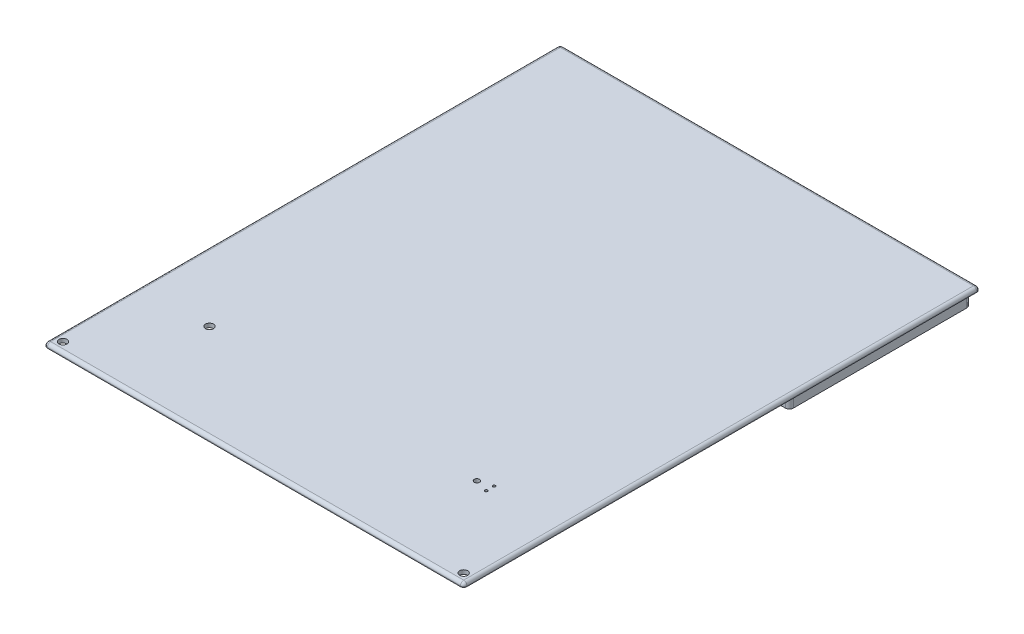
SolidWorks part; units mm, degrees
ref_plane "Front Plane" through (0, 0, 0) normal (0, 0, 1) x (1, 0, 0)
ref_plane "Top Plane" through (0, 0, 0) normal (0, 1, 0) x (1, 0, 0)
ref_plane "Right Plane" through (0, 0, 0) normal (1, 0, 0) x (0, 0, -1)
sketch "Sketch1" plane through (0, 0, 0) normal (0, 1, 0) x (1, 0, 0)
  line L0 (79.25, -36) -> (79.25, 36)
  line L1 (-78, -34.75) -> (78, -34.75)
  line L2 (-78, -34.75) -> (-78, 34.75)
  line L3 (-78, 34.75) -> (78, 34.75)
  line L4 (78, -34.75) -> (78, 34.75)
  line L5 (-78, -34.75) -> (78, 34.75) construction
  line L6 (-78, 34.75) -> (78, -34.75) construction
  line L7 (-79.25, 36) -> (79.25, 36)
  line L8 (-79.25, -36) -> (-79.25, 36)
  line L9 (-78, -36) -> (78, -36)
  line L10 (-78, -36) -> (-78, -86)
  line L11 (-78, -36) -> (78, -36)
  line L12 (-79.25, -36) -> (-79.25, -86)
  line L13 (-79.25, -86) -> (-79.25, -159)
  line L14 (79.25, -36) -> (79.25, -86)
  line L15 (78, -36) -> (78, -86)
  line L16 (-79.25, -36) -> (79.25, -36) construction
  line L17 (-78, -86) -> (-78, -100.5886)
  line L18 (79.25, -86) -> (79.25, -159)
  line L19 (78, -86) -> (78, -157.75)
  line L20 (79.25, -159) -> (-79.25, -159)
  line L21 (78, -159) -> (79.25, -159)
  line L22 (-78, -100.5886) -> (-78, -157.75)
  line L23 (-78, -157.75) -> (78, -157.75)
  line L24 (-78, -157.75) -> (78, -157.75) construction
  line L25 (0, -157.75) -> (0, -117.25)
  line L26 (-40, -117.25) -> (40, -117.25)
  line L27 (-34, -117.25) -> (34, -117.25)
  line L28 (-40, -117.25) -> (-34, -117.25) construction
  circle A0 centre (-37, -117.25) radius 3
  point P0 (0, 0)
  point P27 (0, -117.25)
  point P30 (0, -117.25)
  dimension "D1" = 156
  dimension "D2" = 69.5
  dimension "D4" = 50
  dimension "D5" = 195
  dimension "D6" = 1.25
  dimension "D7" = 40.5
  dimension "D8" = 80
  dimension "D9" = 68
  dimension "D3" = 1.25
sketch "Sketch2" plane through (0, 0, 0) normal (0, 1, 0) x (1, 0, 0)
  line L0 (-79.25, 36) -> (79.25, 36)
  line L1 (79.25, 36) -> (79.25, -159)
  line L2 (79.25, -159) -> (-79.25, -159)
  line L3 (-79.25, -159) -> (-79.25, 36)
extrude "Boss-Extrude1" add sketch "Sketch2" against normal blind 1.25
extrude "Boss-Extrude2" add sketch "Sketch1" along normal blind 105 contours L20 L18 L14 L0 L7 L8 L12 L13 L23 L22 L17 L10 L9 L15 L19 L4 L1 L2 L3 region at (78.9987, 0, 61)
sketch "Sketch4" plane through (0, 0, 0) normal (0, 1, 0) x (1, 0, 0)
  line L0 (-78, -157.75) -> (78, -157.75) construction
  line L1 (0, -157.75) -> (0, -117.75)
  line L2 (0, -5.0875) -> (0, 5.0875) construction
  line L3 (-34, -117.75) -> (34, -117.75)
  line L4 (-40.15, -117.75) -> (-39.575, -117.75)
  line L5 (-40.15, -117.75) -> (-39.575, -117.75) construction
  line L6 (34, -117.75) -> (34.575, -117.75) construction
  line L7 (-34.575, -117.75) -> (34.575, -117.75)
  line L8 (-34.575, -117.75) -> (-34, -117.75) construction
  line L9 (39.575, -117.75) -> (40.15, -117.75) construction
  line L10 (39.575, -117.75) -> (40.15, -117.75)
  circle A0 centre (-37.075, -117.75) radius 2.5
  circle A1 centre (37.075, -117.75) radius 2.5
  point P12 (0, -117.75)
  point P15 (0, -117.75)
  dimension "D1" = 40
  dimension "D2" = 68
  dimension "D3" = 80.3
extrude "Boss-Extrude3" add sketch "Sketch4" along normal blind 8 contours A0 | A1 region at (37.075, 0, 117.75) region at (-37.075, 0, 117.75)
fillet "Fillet2" radius 2 18 edges at (-78, 0, 0) (0, 0, -34.75) (78, 0, 0) (0, 0, 34.75) (0, 0, 36) (78, 0, 96.875) (0, 0, 157.75) (-78, 0, 96.875) (-37.075, 0, 115.25) (37.075, 0, 115.25) (78, 52.5, -34.75) (-78, 52.5, -34.75) (78, 52.5, 34.75) (-78, 52.5, 34.75) (-78, 52.5, 157.75) (78, 52.5, 157.75) (78, 52.5, 36) (-78, 52.5, 36)
sketch "Sketch5" plane through (0, 0, 36) normal (0, 0, 1) x (1, 0, 0)
  line L0 (-76, 105) -> (76, 105) construction
  line L2 (-76, 105) -> (-76, 2) construction
  line L3 (-58.75, 4.5) -> (58.75, 4.5)
  line L4 (-58.75, 4.5) -> (-58.75, 101.5)
  line L5 (-58.75, 101.5) -> (58.75, 101.5)
  line L6 (58.75, 4.5) -> (58.75, 101.5)
  line L7 (-58.75, 53) -> (58.75, 53)
  line L8 (-53.75, 101.5) -> (-53.75, 98)
  line L14 (-58.75, 98) -> (-53.75, 98)
  line L15 (0, 53) -> (0, 77.907)
  circle A0 centre (-53.75, 98) radius 1.55
  circle A1 centre (-53.75, 8) radius 1.55
  circle A2 centre (53.75, 8) radius 1.55
  circle A3 centre (53.75, 98) radius 1.55
  point P8 (0, 53.5)
  dimension "D1" = 97
  dimension "D2" = 117.5
  dimension "D3" = 17.25
  dimension "D4" = 3.5
  dimension "D5" = 5
  dimension "D6" = 3.5
extrude "Cut-Extrude1" cut sketch "Sketch5" against normal blind 8 contours L14 A0 L8 | L8 A0 L14 | A3 | A1 | A2 region at (-54.4078, 98.6578, 36) region at (-53.5307, 97.7807, 36) region at (-53.75, 8, 36) region at (53.75, 98, 36)
sketch "Sketch6" plane through (0, 0, 157.75) normal (0, 0, -1) x (-1, 0, 0)
  line L0 (-76, 2) -> (76, 2) construction
  line L1 (0, 2) -> (0, 22)
  line L2 (0, 5.0875) -> (0, -5.0875) construction
  circle A0 centre (0, 22) radius 8.25
  dimension "D1" = 20
extrude "Cut-Extrude2" cut sketch "Sketch6" against normal blind 8 contours A0 region at (-5.6686, 16.3314, 157.75)
sketch "Sketch8" plane through (-79.25, 0, 0) normal (-1, 0, 0) x (0, 0, 1)
  line L0 (159, 55) -> (116.5, 55)
  line L1 (159, -1.25) -> (159, 105) construction
  line L2 (116.5, 5) -> (116.5, 105)
  line L3 (159, 105) -> (-36, 105) construction
  line L4 (116.5, 55) -> (101.5, 55)
  line L5 (116.5, 55) -> (131.5, 55)
  line L7 (113, 58) -> (120, 58)
  line L8 (113, 58) -> (113, 72)
  line L9 (113, 72) -> (120, 72)
  line L10 (120, 58) -> (120, 72)
  line L11 (113, 58) -> (120, 72) construction
  line L12 (113, 72) -> (120, 58) construction
  circle A0 centre (101.5, 55) radius 3
  circle A1 centre (101.5, 65) radius 3
  circle A2 centre (101.5, 75) radius 3
  circle A3 centre (101.5, 85) radius 3
  circle A4 centre (131.5, 55) radius 3.75
  circle A5 centre (131.5, 75) radius 3.75
  point P9 (116.5, 55)
  point P13 (116.5, 65)
  dimension "D4" = 4
  dimension "D5" = 2
  dimension "D1" = 42.5
  dimension "D2" = 15
  dimension "D3" = 15
  dimension "D6" = 7
  dimension "D7" = 14
  dimension "D8" = 10
  dimension "D9" = 50
extrude "Cut-Extrude3" cut sketch "Sketch8" against normal blind 8 contours A0 | A2 | A3 | A1 | A5 | L8 L9 L10 L7 | A4 region at (-79.25, 55, 98.5849) region at (-79.25, 65, 101.5) region at (-79.25, 75, 101.5) region at (-79.25, 85, 101.5) region at (-79.25, 75, 131.5)
fillet "Fillet3" radius 1.25 4 edges at (0, -1.25, 159) (79.25, -1.25, 61.5) (0, -1.25, -36) (-79.25, -1.25, 61.5)
fillet "Fillet4" radius 1.25 8 edges at (-78.8839, -0.8839, 158.6339) (78.8839, -0.8839, 158.6339) (78.8839, -0.8839, -35.6339) (-78.8839, -0.8839, -35.6339) (-79.25, 52.5, 159) (79.25, 52.5, 159) (79.25, 52.5, -36) (-79.25, 52.5, -36)
sketch "Sketch11" plane through (79.25, 0, 0) normal (1, 0, 0) x (0, 0, -1)
  line L0 (-157.75, 105) -> (34.75, 0) construction
  line L1 (34.75, 105) -> (-157.75, 0)
  line L2 (87.175, 0) -> (-87.175, 0) construction
  line L4 (-111.5, 102.5) -> (-11.5, 102.5)
  line L5 (-111.5, 102.5) -> (-111.5, 2.5)
  line L6 (-111.5, 2.5) -> (-11.5, 2.5)
  line L7 (-11.5, 102.5) -> (-11.5, 2.5)
  line L8 (-111.5, 102.5) -> (-11.5, 2.5) construction
  line L9 (-111.5, 2.5) -> (-11.5, 102.5) construction
  line L10 (-99, 15) -> (-24, 15)
  line L11 (-99, 15) -> (-99, 90)
  line L12 (-99, 90) -> (-24, 90)
  line L13 (-24, 15) -> (-24, 90)
  line L14 (-99, 15) -> (-24, 90) construction
  line L15 (-99, 90) -> (-24, 15) construction
  circle A0 centre (-11.5, 102.5) radius 1.55
  circle A1 centre (-111.5, 102.5) radius 1.55
  circle A2 centre (-99, 90) radius 1.55
  circle A3 centre (-24, 90) radius 1.55
  circle A4 centre (-99, 15) radius 1.55
  circle A5 centre (-111.5, 2.5) radius 1.55
  circle A6 centre (-11.5, 2.5) radius 1.55
  circle A7 centre (-24, 15) radius 1.55
  point P9 (-61.5, 52.5)
  point P14 (-61.5, 52.5)
  dimension "D1" = 100
  dimension "D2" = 100
  dimension "D3" = 75
  dimension "D4" = 75
extrude "Cut-Extrude4" cut sketch "Sketch11" against normal blind 8 contours L7 A0 L4 | L4 A0 L7 | L13 A3 L12 | L12 A3 L13 | L6 A6 L7 | L5 A5 L6 | L6 A5 L5 | L11 A4 L10 | L10 A4 L11 | L10 A7 L13 | L13 A7 L10 | A1 | A2 | A6 region at (79.25, 101.8422, 12.1578) region at (79.25, 102.7193, 11.2807) region at (79.25, 2.2807, 11.2807) region at (79.25, 14.7807, 23.7807) region at (79.25, 15.6578, 24.6578) region at (79.25, 89.3422, 24.6578) region at (79.25, 90.2193, 23.7807) region at (79.25, 15.6578, 98.3422) region at (79.25, 14.7807, 99.2193) region at (79.25, 2.2807, 111.7193) region at (79.25, 3.1578, 110.8422)
sketch "Sketch12" plane through (0, 105, 0) normal (0, 1, 0) x (1, 0, 0)
  line L0 (0, -155.75) -> (0, -144.3132)
  line L1 (-78, -157.75) -> (-73, -157.75)
  line L2 (-78, -157.75) -> (-78, -152.75)
  line L3 (-78, -152.75) -> (-73, -152.75)
  line L4 (-73, -157.75) -> (-73, -152.75)
  line L5 (-76, -155.75) -> (76, -155.75) construction
  line L6 (0, -5.0875) -> (0, 5.0875) construction
  line L7 (78, -152.75) -> (73, -152.75)
  line L8 (73, -157.75) -> (73, -152.75)
  line L9 (78, -157.75) -> (73, -157.75)
  line L10 (78, -157.75) -> (78, -152.75)
  line M6 (76, -157.75) -> (-76, -157.75)
  arc M7 (-76, -157.75) -> (-78, -155.75) centre (-76, -155.75) cw
  line M8 (-78, -155.75) -> (-78, -38)
  line M12 (78, -38) -> (78, -155.75)
  arc M13 (78, -155.75) -> (76, -157.75) centre (76, -155.75) cw
  dimension "D1" = 5
  dimension "D2" = 5
extrude "Boss-Extrude5" add sketch "Sketch12" against normal up to surface (105 mm away) contours L8 L7 M6 M13 M12 | L4 L3 M6 M8 M7 region at (75.427, 105, 155.177) region at (-75.427, 105, 155.177) up to face at (0, 0, 96.875)
fillet "Fillet5" radius 1.25 14 edges at (78, 53.5, 152.75) (77.4142, 0.5858, 152.75) (74.5, 0, 152.75) (73, 0, 154.25) (73, 0.5858, 157.1642) (-73, 0, 154.25) (-73, 0.5858, 157.1642) (-74.5, 0, 152.75) (-77.4142, 0.5858, 152.75) (73, 53.5, 157.75) (73, 52.5, 152.75) (-73, 53.5, 157.75) (-78, 53.5, 152.75) (-73, 52.5, 152.75)
sketch "Sketch14" plane through (0, 105, 0) normal (0, 1, 0) x (1, 0, 0)
  line L0 (78, -38) -> (78, -151.5) construction
  line L1 (73.3661, -153.1161) -> (78, -153.1161)
  line L2 (73.3661, -153.1161) -> (73.3661, -157.75)
  line L3 (73.3661, -157.75) -> (78, -157.75)
  line L4 (78, -153.1161) -> (78, -157.75)
  line L5 (73.3661, -153.1161) -> (78, -157.75) construction
  line L6 (78, -157.75) -> (78.0536, -157.7607) construction
  line L7 (0, -157.75) -> (0, -147.0716)
  line L8 (-71.75, -157.75) -> (71.75, -157.75) construction
  line L9 (0, -58.4375) -> (0, 58.4375) construction
  arc A0 (74.25, -152.75) -> (73, -154) centre (74.25, -154) ccw construction
  circle A1 centre (75.6831, -155.4331) radius 1.525
  circle A2 centre (-75.6831, -155.4331) radius 1.525
extrude "Cut-Extrude5" cut sketch "Sketch14" against normal blind 8 contours A1 | A2 region at (75.6831, 105, 155.4331) region at (-75.6831, 105, 155.4331)
sketch "Sketch15" plane through (0, 105, 0) normal (0, 1, 0) x (1, 0, 0)
  line L16 (76, 33) -> (-76, 33)
  line L17 (-76.25, 32.75) -> (-76.25, -32.75)
  line L18 (-76, -33) -> (76, -33)
  line L19 (76.25, -32.75) -> (76.25, 32.75)
  line L20 (-77.5, 32.75) -> (-77.5, -32.75)
  line L21 (-76, -34.25) -> (76, -34.25)
  line L22 (77.5, -32.75) -> (77.5, 32.75)
  line L23 (76, 34.25) -> (-76, 34.25)
  line L24 (-77.5, 32.75) -> (-77.5, -32.75)
  line L25 (-76, -34.25) -> (76, -34.25)
  line L26 (77.5, -32.75) -> (77.5, 32.75)
  line L27 (76, 34.25) -> (-76, 34.25)
  arc A8 (78, 32.75) -> (76, 34.75) centre (76, 32.75) ccw construction
  arc A17 (-76, 33) -> (-76.25, 32.75) centre (-76, 32.75) ccw
  arc A18 (-76.25, -32.75) -> (-76, -33) centre (-76, -32.75) ccw
  arc A19 (76, -33) -> (76.25, -32.75) centre (76, -32.75) ccw
  arc A20 (76.25, 32.75) -> (76, 33) centre (76, 32.75) ccw
  arc A21 (-76, 34.25) -> (-77.5, 32.75) centre (-76, 32.75) ccw
  arc A22 (-77.5, -32.75) -> (-76, -34.25) centre (-76, -32.75) ccw
  arc A23 (76, -34.25) -> (77.5, -32.75) centre (76, -32.75) ccw
  arc A24 (77.5, 32.75) -> (76, 34.25) centre (76, 32.75) ccw
  arc A25 (-76, 34.25) -> (-77.5, 32.75) centre (-76, 32.75) ccw
  arc A26 (-77.5, -32.75) -> (-76, -34.25) centre (-76, -32.75) ccw
  arc A27 (76, -34.25) -> (77.5, -32.75) centre (76, -32.75) ccw
  arc A28 (77.5, 32.75) -> (76, 34.25) centre (76, 32.75) ccw
  dimension "D1" = 0.5
  dimension "D2" = 1.25
extrude "Boss-Extrude6" add sketch "Sketch15" against normal blind 5 separate body
sketch "Sketch19" plane through (0, 105, 0) normal (0, 1, 0) x (1, 0, 0)
  circle A2 centre (75.6831, -155.4331) radius 1.525
  circle A3 centre (75.6831, -155.4331) radius 1.525
  circle A5 centre (-75.6831, -155.4331) radius 1.525
  circle A6 centre (-75.6831, -155.4331) radius 1.525
  dimension "D1" = 0
  dimension "D2" = 0
extrude "Cut-Extrude10" cut sketch "Sketch19" along normal blind 176.5 and the other way blind 9
sketch "Sketch16" plane through (0, 105, 0) normal (0, 1, 0) x (1, 0, 0)
  line L8 (-79.25, 34.75) -> (-79.25, -157.75)
  line L9 (-78, -159) -> (78, -159)
  line L10 (79.25, -157.75) -> (79.25, 34.75)
  line L11 (78, 36) -> (-78, 36)
  line L12 (-79.25, 34.75) -> (-79.25, -157.75)
  line L13 (-78, -159) -> (78, -159)
  line L14 (79.25, -157.75) -> (79.25, 34.75)
  line L15 (78, 36) -> (-78, 36)
  arc A8 (-79.25, -157.75) -> (-78, -159) centre (-78, -157.75) ccw
  arc A9 (78, -159) -> (79.25, -157.75) centre (78, -157.75) ccw
  arc A10 (79.25, 34.75) -> (78, 36) centre (78, 34.75) ccw
  arc A11 (-78, 36) -> (-79.25, 34.75) centre (-78, 34.75) ccw
  arc A12 (-79.25, -157.75) -> (-78, -159) centre (-78, -157.75) ccw
  arc A13 (78, -159) -> (79.25, -157.75) centre (78, -157.75) ccw
  arc A14 (79.25, 34.75) -> (78, 36) centre (78, 34.75) ccw
  arc A15 (-78, 36) -> (-79.25, 34.75) centre (-78, 34.75) ccw
  dimension "D1" = 0
extrude "Boss-Extrude7" add sketch "Sketch16" along normal blind 1.5
sketch "Sketch17" plane through (0, 105, 0) normal (0, -1, 0) x (1, 0, 0)
  line L5 (97.501, -101.5148) -> (-116.8928, -101.5148)
  line L6 (97.501, -101.5148) -> (97.501, 210.2358)
  line L7 (97.501, 210.2358) -> (-116.8928, 210.2358)
  line L8 (78, -32.75) -> (78, 32.75)
  line L9 (76, 34.75) -> (-76, 34.75)
  line L10 (-78, 32.75) -> (-78, -32.75)
  line L11 (-76, -34.75) -> (76, -34.75)
  line L12 (78, -32.75) -> (78, 32.75)
  line L13 (76, 34.75) -> (-76, 34.75)
  line L14 (-78, 32.75) -> (-78, -32.75)
  line L15 (-76, -34.75) -> (76, -34.75)
  line L16 (-116.8928, -101.5148) -> (-116.8928, 210.2358)
  line L17 (97.501, -101.5148) -> (-116.8928, 210.2358) construction
  line L18 (97.501, 210.2358) -> (-116.8928, -101.5148) construction
  arc A8 (78, 32.75) -> (76, 34.75) centre (76, 32.75) ccw
  arc A9 (-76, 34.75) -> (-78, 32.75) centre (-76, 32.75) ccw
  arc A10 (-78, -32.75) -> (-76, -34.75) centre (-76, -32.75) ccw
  arc A11 (76, -34.75) -> (78, -32.75) centre (76, -32.75) ccw
  arc A12 (78, 32.75) -> (76, 34.75) centre (76, 32.75) ccw
  arc A13 (-76, 34.75) -> (-78, 32.75) centre (-76, 32.75) ccw
  arc A14 (-78, -32.75) -> (-76, -34.75) centre (-76, -32.75) ccw
  arc A15 (76, -34.75) -> (78, -32.75) centre (76, -32.75) ccw
  point P2 (-9.6959, 54.3605)
  dimension "D1" = 0
extrude "Cut-Extrude6" cut sketch "Sketch17" along normal blind 142.5
sketch "Sketch18" plane through (0, 100, 0) normal (0, -1, 0) x (1, 0, 0)
  line L1 (-421.9306, -105.0953) -> (421.9306, -105.0953)
  line L2 (-421.9306, -105.0953) -> (-421.9306, 105.0953)
  line L3 (-421.9306, 105.0953) -> (421.9306, 105.0953)
  line L4 (421.9306, -105.0953) -> (421.9306, 105.0953)
  line L5 (-421.9306, -105.0953) -> (421.9306, 105.0953) construction
  line L6 (-421.9306, 105.0953) -> (421.9306, -105.0953) construction
  point P0 (0, 0)
extrude "Cut-Extrude7" cut sketch "Sketch18" along normal blind 211.5
fillet "Fillet6" radius 1.25 8 edges at (0, 106.5, -36) (78.8839, 106.5, -35.6339) (79.25, 106.5, 61.5) (78.8839, 106.5, 158.6339) (0, 106.5, 159) (-78.8839, 106.5, 158.6339) (-79.25, 106.5, 61.5) (-78.8839, 106.5, -35.6339)
sketch "Sketch21" plane through (0, 106.5, 0) normal (0, 1, 0) x (1, 0, 0)
  line L0 (-78.8839, -158.6339) -> (-75.6807, -155.4307)
  line L1 (0, -159) -> (0, -145.5027)
  line L2 (78, -159) -> (-78, -159) construction
  line L3 (0, -3.575) -> (0, 3.575) construction
  arc A0 (-79.25, -157.75) -> (-78, -159) centre (-78, -157.75) ccw construction
  circle A1 centre (-75.6807, -155.4307) radius 1.525
  circle A2 centre (75.6807, -155.4307) radius 1.525
  dimension "D1" = 4.53
extrude "Cut-Extrude11" cut sketch "Sketch21" against normal blind 46.5 contours A1 | A2
sketch "Sketch22" plane through (0, 106.5, 0) normal (0, 1, 0) x (1, 0, 0)
  line L0 (53, -122.75) -> (-53, -122.75)
  line L1 (-78, -157.75) -> (-53, -157.75)
  line L2 (-78, -157.75) -> (-78, -122.75)
  line L3 (-78, -122.75) -> (-53, -122.75)
  line L4 (-53, -157.75) -> (-53, -122.75)
  line L6 (53, -124.25) -> (53, -121.25)
  line L7 (53, -122.75) -> (48, -122.75)
  circle A0 centre (-53, -122.75) radius 1.525
  circle A1 centre (53, -121.25) radius 0.5
  circle A2 centre (53, -124.25) radius 0.5
  circle A3 centre (48, -122.75) radius 1
  point P9 (0, -122.75)
  point P11 (53, -122.75)
  dimension "D3" = 3
  dimension "D4" = 5
  dimension "D1" = 25
  dimension "D2" = 35
extrude "Cut-Extrude12" cut sketch "Sketch22" against normal blind 46.5 contours L3 A0 L4 | L4 A0 L3 | A2 | A1 | L7 A3 L0 | L0 A3 L7 | L4 A0 L0 region at (-52.3528, 106.5, 123.3972) region at (-53, 106.5, 122.1028) region at (48, 106.5, 123.1744) region at (48, 106.5, 122.3256) region at (53.3436, 106.5, 123.9064) region at (52.6564, 106.5, 120.9064) region at (-53.6472, 106.5, 123.3972)
